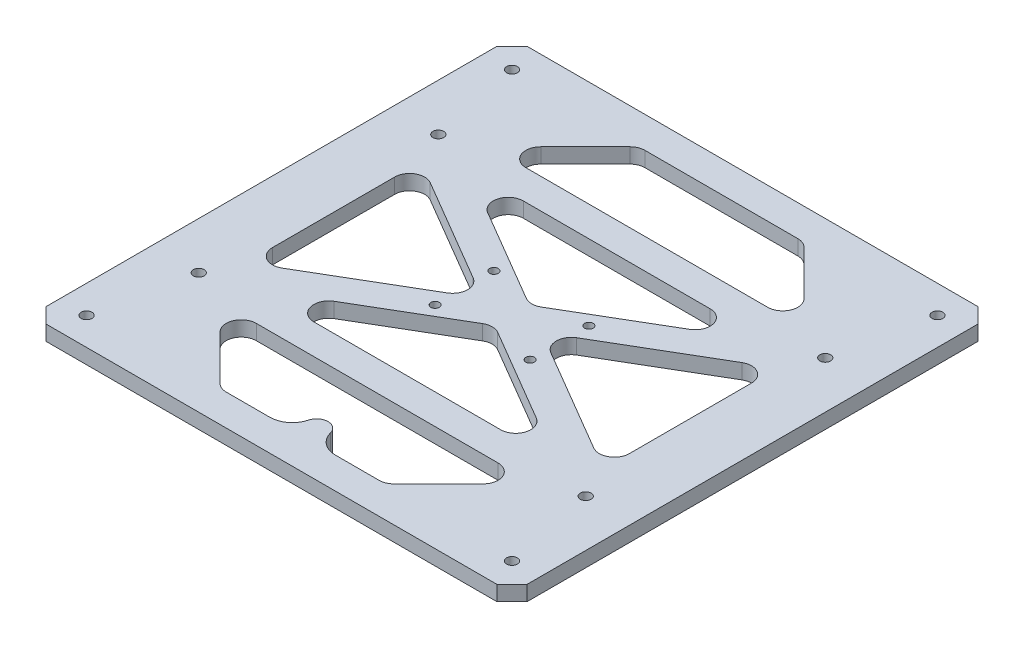
SolidWorks part; units mm, degrees
ref_plane "Front Plane" through (0, 0, 0) normal (0, 0, 1) x (1, 0, 0)
ref_plane "Top Plane" through (0, 0, 0) normal (0, 1, 0) x (1, 0, 0)
ref_plane "Right Plane" through (0, 0, 0) normal (1, 0, 0) x (0, 0, -1)
sketch "Sketch1" plane through (0, 0, 0) normal (0, 1, 0) x (1, 0, 0)
  line L0 (0, 196.85) -> (6.35, 203.2)
  line L1 (6.35, 0) -> (196.85, 0)
  line L2 (0, 6.35) -> (0, 196.85)
  line L3 (6.35, 203.2) -> (196.85, 203.2)
  line L4 (203.2, 6.35) -> (203.2, 196.85)
  line L5 (196.85, 203.2) -> (203.2, 196.85)
  line L6 (196.85, 0) -> (203.2, 6.35)
  line L7 (0, 6.35) -> (6.35, 0)
  point P0 (0, 0)
  point P1 (203.2, 203.2)
  point P2 (0, 203.2)
  point P3 (203.2, 0)
  dimension "D1" = 203.2
  dimension "D2" = 203.2
extrude "Boss-Extrude1" add sketch "Sketch1" along normal blind 6.35
sketch "Sketch3" plane through (0, 6.35, 0) normal (0, 1, 0) x (1, 0, 0)
  line L0 (6.35, 0) -> (196.85, 0) construction
  line L1 (0, 196.85) -> (0, 6.35) construction
  line L2 (203.2, 6.35) -> (203.2, 196.85) construction
  line L3 (196.85, 203.2) -> (6.35, 203.2) construction
  circle A0 centre (11.7373, 11.7373) radius 2.286
  circle A1 centre (191.4627, 11.7373) radius 2.286
  circle A2 centre (191.4627, 191.4627) radius 2.286
  circle A3 centre (11.7373, 191.4627) radius 2.286
  dimension "D1" = 2
  dimension "D3" = 4.572
  dimension "D4" = 11.7373
  dimension "D5" = 11.7373
  dimension "D6" = 11.7373
  dimension "D7" = 11.7373
  dimension "D8" = 11.7373
  dimension "D2" = 2
extrude "Cut-Extrude2" cut sketch "Sketch3" against normal through all
sketch "Sketch4" plane through (0, 6.35, 0) normal (0, 1, 0) x (1, 0, 0)
  line L0 (0, 196.85) -> (0, 6.35) construction
  line L1 (19.8692, 152.1955) -> (183.3308, 152.1955) construction
  line L2 (19.8692, 152.1955) -> (19.8692, 51.0045) construction
  line L3 (19.8692, 51.0045) -> (183.3308, 51.0045) construction
  line L4 (183.3308, 152.1955) -> (183.3308, 51.0045) construction
  line L5 (196.85, 203.2) -> (6.35, 203.2) construction
  line L6 (16.6942, 140.0403) -> (66.6884, 190.0345)
  line L7 (136.5116, 190.0345) -> (66.6884, 190.0345)
  line L8 (136.5116, 190.0345) -> (186.5058, 140.0403)
  line L9 (186.5058, 63.1597) -> (136.5116, 13.1655)
  line L10 (186.5058, 140.0403) -> (186.5058, 63.1597)
  line L11 (136.5116, 13.1655) -> (66.6884, 13.1655)
  line L12 (66.6884, 13.1655) -> (16.6942, 63.1597)
  line L13 (16.6942, 63.1597) -> (16.6942, 140.0403)
  circle A0 centre (19.8692, 152.1955) radius 2.286
  circle A1 centre (183.3308, 152.1955) radius 2.286
  circle A2 centre (183.3308, 51.0045) radius 2.286
  circle A3 centre (19.8692, 51.0045) radius 2.286
  point P6 (0, 101.6)
  point P7 (19.8692, 101.6)
  point P10 (101.6, 203.2)
  point P11 (101.6, 152.1955)
  dimension "D3" = 4.572
  dimension "D5" = 6.35
  dimension "D7" = 6.35
  dimension "D1" = 163.4617
  dimension "D2" = 101.1911
  dimension "D4" = 6.35
  dimension "D6" = 6.35
  dimension "D8" = 6.35
extrude "Cut-Extrude3" cut sketch "Sketch4" against normal through all
sketch "Sketch5" plane through (0, 6.35, 0) normal (0, 1, 0) x (1, 0, 0)
  line L0 (19.8692, 51.0045) -> (183.3308, 51.0045) construction
  line L1 (183.3308, 51.0045) -> (183.3308, 152.1955) construction
  line L2 (183.3308, 152.1955) -> (19.8692, 152.1955) construction
  line L3 (19.8692, 152.1955) -> (19.8692, 51.0045) construction
  line L4 (189.6808, 158.5455) -> (13.5192, 158.5455)
  line L5 (13.5192, 158.5455) -> (13.5192, 44.6545)
  line L6 (13.5192, 44.6545) -> (189.6808, 44.6545)
  line L7 (189.6808, 44.6545) -> (189.6808, 158.5455)
  line L8 (141.0736, 145.8455) -> (62.1264, 145.8455)
  line L9 (26.2192, 127.3922) -> (26.2192, 75.8078)
  line L10 (62.1264, 57.3545) -> (141.0736, 57.3545)
  line L11 (176.9808, 75.8078) -> (176.9808, 127.3922)
  line L12 (26.2192, 57.3545) -> (176.9808, 145.8455) construction
  line L13 (176.9808, 57.3545) -> (26.2192, 145.8455) construction
  line L14 (58.912, 69.1808) -> (98.3856, 92.3502)
  line L15 (167.4165, 70.3314) -> (123.4744, 96.1237)
  line L16 (35.7835, 70.3314) -> (79.7256, 96.1237)
  line L17 (144.288, 69.1808) -> (104.8144, 92.3502)
  line L18 (180.1952, 62.8308) -> (29.4335, 151.3219) construction
  line L19 (173.7665, 51.8781) -> (23.0048, 140.3692) construction
  line L20 (23.0048, 62.8308) -> (173.7665, 151.3219) construction
  line L21 (29.4335, 51.8781) -> (180.1952, 140.3692) construction
  line L22 (26.2192, 57.3545) -> (176.9808, 57.3545) construction
  line L23 (176.9808, 57.3545) -> (176.9808, 145.8455) construction
  line L24 (176.9808, 145.8455) -> (26.2192, 145.8455) construction
  line L25 (26.2192, 145.8455) -> (26.2192, 57.3545) construction
  line L26 (79.7256, 107.0763) -> (35.7835, 132.8686)
  line L27 (104.8144, 110.8498) -> (144.288, 134.0192)
  line L28 (123.4744, 107.0763) -> (167.4165, 132.8686)
  line L29 (98.3856, 110.8498) -> (58.912, 134.0192)
  circle A0 centre (183.3308, 51.0045) radius 2.286 construction
  circle A1 centre (183.3308, 152.1955) radius 2.286 construction
  circle A2 centre (19.8692, 152.1955) radius 2.286 construction
  circle A3 centre (19.8692, 51.0045) radius 2.286 construction
  circle A4 centre (183.3308, 51.0045) radius 2.286
  circle A5 centre (183.3308, 152.1955) radius 2.286
  circle A6 centre (19.8692, 152.1955) radius 2.286
  circle A7 centre (19.8692, 51.0045) radius 2.286
  arc A8 (58.912, 134.0192) -> (62.1264, 145.8455) centre (62.1264, 139.4955) cw
  arc A9 (144.288, 134.0192) -> (141.0736, 145.8455) centre (141.0736, 139.4955) ccw
  arc A10 (167.4165, 132.8686) -> (176.9808, 127.3922) centre (170.6308, 127.3922) cw
  arc A11 (123.4744, 107.0763) -> (123.4744, 96.1237) centre (126.6888, 101.6) ccw
  arc A12 (167.4165, 70.3314) -> (176.9808, 75.8078) centre (170.6308, 75.8078) ccw
  arc A13 (144.288, 69.1808) -> (141.0736, 57.3545) centre (141.0736, 63.7045) cw
  arc A14 (104.8144, 92.3502) -> (98.3856, 92.3502) centre (101.6, 86.8739) ccw
  arc A15 (79.7256, 107.0763) -> (79.7256, 96.1237) centre (76.5112, 101.6) cw
  arc A16 (35.7835, 132.8686) -> (26.2192, 127.3922) centre (32.5692, 127.3922) ccw
  arc A17 (35.7835, 70.3314) -> (26.2192, 75.8078) centre (32.5692, 75.8078) cw
  arc A18 (58.912, 69.1808) -> (62.1264, 57.3545) centre (62.1264, 63.7045) ccw
  arc A19 (98.3856, 110.8498) -> (104.8144, 110.8498) centre (101.6, 116.3261) ccw
  dimension "D5" = 6.35
  dimension "D6" = 6.35
  dimension "D1" = 6.35
  dimension "D3" = 6.35
  dimension "D2" = 6.35
  dimension "D4" = 6.35
extrude "Boss-Extrude2" add sketch "Sketch5" against normal up to surface (6.35 mm away) up to face at (183.3308, 0, -149.9095)
fillet "Fillet1" radius 6.35 8 edges at (136.5116, 3.175, -190.0345) (66.6884, 3.175, -190.0345) (35.1994, 3.175, -158.5455) (168.0006, 3.175, -158.5455) (66.6884, 3.175, -13.1655) (35.1994, 3.175, -44.6545) (136.5116, 3.175, -13.1655) (168.0006, 3.175, -44.6545)
sketch "Sketch6" plane through (0, 6.35, 0) normal (0, 1, 0) x (1, 0, 0)
  line L0 (6.35, 0) -> (196.85, 0) construction
  line L1 (69.3186, 13.1655) -> (133.8814, 13.1655) construction
  line L2 (87.7184, 13.1655) -> (115.4816, 13.1655)
  circle A0 centre (101.6, 19.05) radius 2.286 construction
  arc A1 (106.2681, 20.2742) -> (96.9319, 20.2742) centre (101.6, 19.05) ccw
  arc A2 (87.7184, 13.1655) -> (96.9319, 20.2742) centre (87.7184, 22.6905) ccw
  arc A3 (106.2681, 20.2742) -> (115.4816, 13.1655) centre (115.4816, 22.6905) ccw
  point P7 (101.6, 0)
  dimension "D1" = 19.05
  dimension "D2" = 4.572
  dimension "D3" = 2.54
  dimension "D4" = 19.05
extrude "Boss-Extrude3" add sketch "Sketch6" against normal up to surface (6.35 mm away) up to face at (101.6, 0, -26.9283)
sketch "Sketch8" plane through (0, 0, 0) normal (0, 1, 0) x (1, 0, 0)
  circle A0 centre (101.6, 19.05) radius 4.826
  circle A1 centre (101.6, 19.05) radius 2.286
  arc A2 (106.2681, 20.2742) -> (96.9319, 20.2742) centre (101.6, 19.05) ccw construction
  dimension "D1" = 4.572
extrude "Boss-Extrude4" add sketch "Sketch8" against normal blind 6.35
sketch "Sketch9" plane through (0, 0, 0) normal (0, 1, 0) x (1, 0, 0)
  line L0 (80.0033, 114.9695) -> (123.1967, 88.2305) construction
  line L1 (123.1967, 114.9695) -> (80.0033, 88.2305) construction
  circle A0 centre (121.6633, 114.0202) radius 1.8034 construction
  circle A1 centre (81.5367, 114.0202) radius 1.8034 construction
  circle A2 centre (81.5367, 89.1798) radius 1.8034 construction
  circle A3 centre (121.6633, 89.1798) radius 1.8034 construction
  circle A4 centre (81.5367, 114.0202) radius 3.8354
  circle A5 centre (121.6633, 114.0202) radius 3.8354
  circle A6 centre (121.6633, 89.1798) radius 3.8354
  circle A7 centre (81.5367, 89.1798) radius 3.8354
  point P8 (101.6, 101.6)
  point P17 (0, 0)
  point P18 (0, 0)
  point P19 (0, 0)
  point P20 (0, 0)
  point P21 (0, 0)
  point P22 (0, 0)
  dimension "D1" = 3.6068
  dimension "D2" = 50.8
  dimension "D3" = 116.481
  dimension "D4" = 2.032
extrude "Cut-Extrude4" cut sketch "Sketch9" along normal offset from surface (3.81 mm away) 2.54 up to face at (101.6, 6.35, -23.5639)
sketch "Sketch10" plane through (0, 3.81, 0) normal (0, -1, 0) x (-1, 0, 0)
  circle A26 centre (-81.5367, 114.0202) radius 1.8034
  circle A27 centre (-121.6633, 114.0202) radius 1.8034
  circle A28 centre (-121.6633, 89.1798) radius 1.8034
  circle A29 centre (-81.5367, 89.1798) radius 1.8034
  dimension "D1" = 3.6068
extrude "Cut-Extrude5" cut sketch "Sketch10" against normal through all
